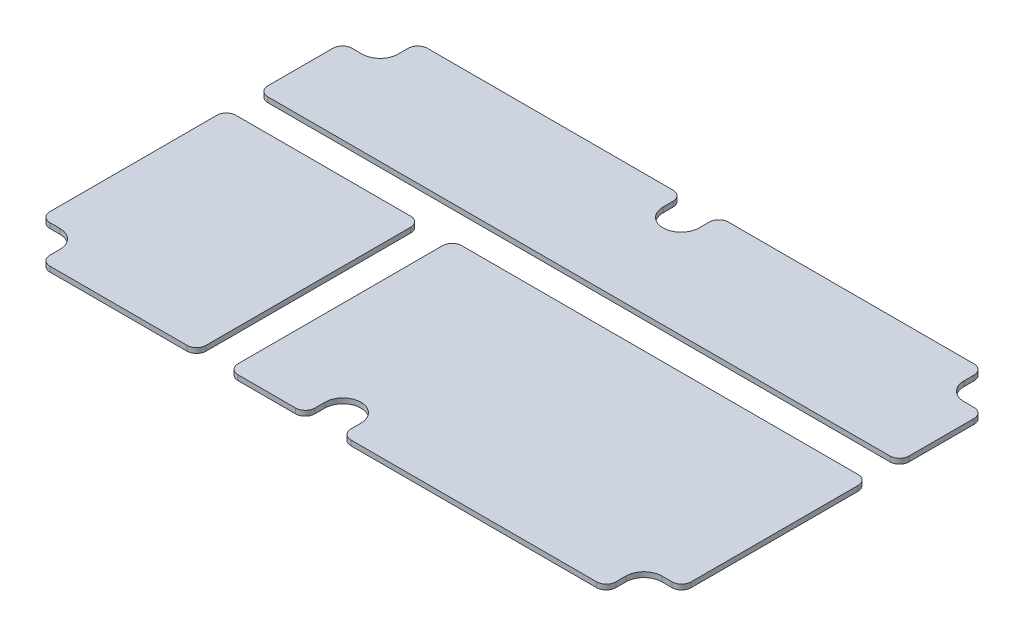
SolidWorks part; units mm, degrees
ref_plane "Front Plane" through (0, 0, 0) normal (0, 0, 1) x (1, 0, 0)
ref_plane "Top Plane" through (0, 0, 0) normal (0, 1, 0) x (1, 0, 0)
ref_plane "Right Plane" through (0, 0, 0) normal (1, 0, 0) x (0, 0, -1)
ref_axis "L-R Axis" through (-88.99, 0, 0) along (1, 0, 0)
ref_axis "U-D Axis" through (0, 55, 0) along (0, -1, 0)
ref_axis "I-O Axis" through (0, 0, -88.99) along (0, 0, 1)
sketch "Sketch1" plane through (0, 0, 0) normal (0, 1, 0) x (1, 0, 0)
  line L0 (8.6561, -59.0563) -> (85.5408, -59.0563)
  line L1 (-85.5408, 59.0563) -> (-8.6561, 59.0563)
  line L2 (-100.3313, 44.2626) -> (-100.3313, 23.9437)
  line L3 (-97.3313, 20.9437) -> (97.3313, 20.9437)
  line L4 (100.3313, 44.2626) -> (100.3313, 23.9437)
  line L5 (-97.3313, 10.9437) -> (-42.6687, 10.9437)
  line L6 (-100.3313, 7.9437) -> (-100.3313, -44.2626)
  line L7 (-85.5408, -59.0563) -> (-42.6687, -59.0563)
  line L8 (-39.6687, 7.9437) -> (-39.6687, -56.0563)
  line L9 (-26.6687, 10.9437) -> (97.3313, 10.9437)
  line L10 (-29.6687, 7.9437) -> (-29.6687, -56.0563)
  line L11 (-26.6687, -59.0563) -> (-8.6561, -59.0563)
  line L12 (100.3313, 7.9437) -> (100.3313, -44.2626)
  line L13 (8.6561, 59.0563) -> (85.5408, 59.0563)
  line L14 (94.1969, -47.2626) -> (97.3313, -47.2626)
  line L15 (100.3313, -47.2626) -> (100.3313, 10.9437)
  line L16 (97.3313, 47.2626) -> (94.1969, 47.2626)
  line L17 (88.5408, 52.9188) -> (88.5408, 56.0563)
  line L18 (88.5408, 59.0563) -> (5.6561, 59.0563)
  line L19 (5.6561, 56.0563) -> (5.6561, 52.9188)
  line L20 (-5.6561, 52.9188) -> (-5.6561, 56.0563)
  line L21 (-5.6561, 59.0563) -> (-88.5408, 59.0563)
  line L22 (-88.5408, 56.0563) -> (-88.5408, 52.9188)
  line L23 (-94.1969, 47.2626) -> (-97.3313, 47.2626)
  line L24 (-100.3313, 47.2626) -> (-100.3313, 20.9437)
  line L25 (-97.3313, -47.2626) -> (-94.1969, -47.2626)
  line L26 (-88.5408, -52.9188) -> (-88.5408, -56.0563)
  line L27 (-88.5408, -59.0563) -> (-39.6687, -59.0563)
  line L28 (-5.6561, -56.0563) -> (-5.6561, -52.9188)
  line L29 (5.6561, -52.9188) -> (5.6561, -56.0563)
  line L30 (5.6561, -59.0563) -> (88.5408, -59.0563)
  line L31 (88.5408, -56.0563) -> (88.5408, -52.9188)
  line L32 (-100.3313, 10.9437) -> (-100.3313, -47.2626)
  line L33 (100.3313, 20.9437) -> (100.3313, 47.2626)
  line L34 (-29.6687, -59.0563) -> (-5.6561, -59.0563)
  arc A0 (94.1969, -47.2626) -> (88.5408, -52.9188) centre (94.1969, -52.9188) ccw
  arc A1 (88.5408, 52.9188) -> (94.1969, 47.2626) centre (94.1969, 52.9188) ccw
  arc A2 (-5.6561, 52.9188) -> (5.6561, 52.9188) centre (0, 52.9188) ccw
  arc A3 (-94.1969, 47.2626) -> (-88.5408, 52.9188) centre (-94.1969, 52.9188) ccw
  arc A4 (-88.5408, -52.9188) -> (-94.1969, -47.2626) centre (-94.1969, -52.9188) ccw
  arc A5 (0, -47.2626) -> (-5.6561, -52.9188) centre (0, -52.9188) ccw
  arc A6 (5.6561, -52.9188) -> (0, -47.2626) centre (0, -52.9188) ccw
  arc A7 (-100.3313, 23.9437) -> (-97.3313, 20.9437) centre (-97.3313, 23.9437) ccw
  arc A8 (97.3313, 20.9437) -> (100.3313, 23.9437) centre (97.3313, 23.9437) ccw
  arc A9 (97.3313, 10.9437) -> (100.3313, 7.9437) centre (97.3313, 7.9437) cw
  arc A10 (-29.6687, -56.0563) -> (-26.6687, -59.0563) centre (-26.6687, -56.0563) ccw
  arc A11 (-26.6687, 10.9437) -> (-29.6687, 7.9437) centre (-26.6687, 7.9437) ccw
  arc A12 (-42.6687, -59.0563) -> (-39.6687, -56.0563) centre (-42.6687, -56.0563) ccw
  arc A13 (-42.6687, 10.9437) -> (-39.6687, 7.9437) centre (-42.6687, 7.9437) cw
  arc A14 (-97.3313, 10.9437) -> (-100.3313, 7.9437) centre (-97.3313, 7.9437) ccw
  arc A15 (-85.5408, 59.0563) -> (-88.5408, 56.0563) centre (-85.5408, 56.0563) ccw
  arc A16 (-100.3313, 44.2626) -> (-97.3313, 47.2626) centre (-97.3313, 44.2626) cw
  arc A17 (-8.6561, 59.0563) -> (-5.6561, 56.0563) centre (-8.6561, 56.0563) cw
  arc A18 (8.6561, 59.0563) -> (5.6561, 56.0563) centre (8.6561, 56.0563) ccw
  arc A19 (85.5408, 59.0563) -> (88.5408, 56.0563) centre (85.5408, 56.0563) cw
  arc A20 (100.3313, 44.2626) -> (97.3313, 47.2626) centre (97.3313, 44.2626) ccw
  arc A21 (100.3313, -44.2626) -> (97.3313, -47.2626) centre (97.3313, -44.2626) cw
  arc A22 (85.5408, -59.0563) -> (88.5408, -56.0563) centre (85.5408, -56.0563) ccw
  arc A23 (8.6561, -59.0563) -> (5.6561, -56.0563) centre (8.6561, -56.0563) cw
  arc A24 (-8.6561, -59.0563) -> (-5.6561, -56.0563) centre (-8.6561, -56.0563) ccw
  arc A25 (-85.5408, -59.0563) -> (-88.5408, -56.0563) centre (-85.5408, -56.0563) cw
  arc A26 (-100.3313, -44.2626) -> (-97.3313, -47.2626) centre (-97.3313, -44.2626) ccw
  point P62 (0, 0)
  dimension "D1" = 3
  dimension "D2" = 3
extrude "Boss-Extrude1" add sketch "Sketch1" along normal blind 1.6 contours L11 A24 L28 A5 A6 L29 A23 L0 A22 L31 A0 L14 A21 L12 A9 L9 A11 L10 A10 | L6 A26 L25 A4 L26 A25 L7 A12 L8 A13 L5 A14 | L4 A20 L16 A1 L17 A19 L13 A18 L19 A2 L20 A17 L1 A15 L22 A3 L23 A16 L2 A7 L3 A8 region at (34.9259, 0, 23.1959) region at (0, 0, -39.2719) region at (-69.1969, 0, 23.1007)
